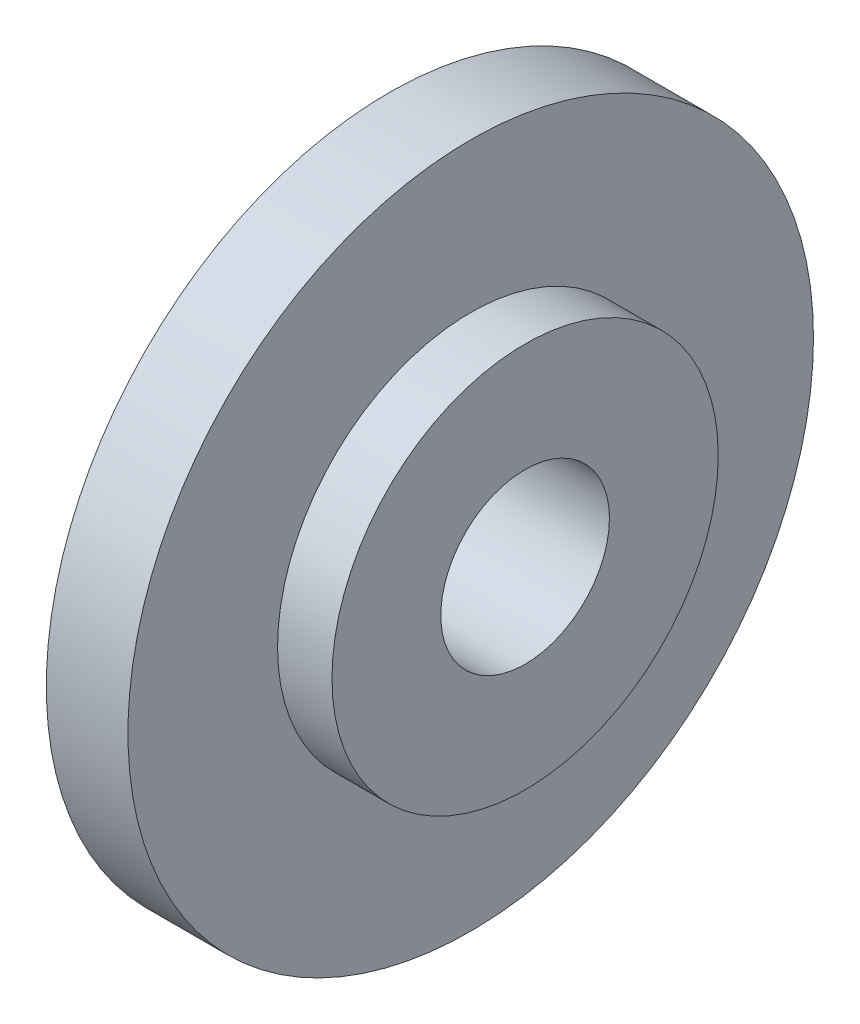
SolidWorks part; units mm, degrees
ref_plane "Front Plane" through (0, 0, 0) normal (0, 0, 1) x (1, 0, 0)
ref_plane "Top Plane" through (0, 0, 0) normal (0, 1, 0) x (1, 0, 0)
ref_plane "Right Plane" through (0, 0, 0) normal (1, 0, 0) x (0, 0, -1)
sketch "Sketch1" plane through (0, 0, 0) normal (1, 0, 0) x (0, 0, -1)
  circle A0 centre (0, 0) radius 12.6
  circle A1 centre (0, 0) radius 7.1
  circle A2 centre (0, 0) radius 3.1
  dimension "D1" = 6.2
  dimension "D2" = 4
  dimension "D3" = 5.5
extrude "Boss-Extrude1" add sketch "Sketch1" along normal blind 3 contours A0 A1 region at (0, 0, 12.2436)
extrude "Boss-Extrude2" add sketch "Sketch1<4>" along normal blind 5 contours A1 A2 region at (0, 0, 6.8992)
sketch "Sketch1<4>" plane through (0, 0, 0) normal (1, 0, 0) x (0, 0, -1) same geometry as "Sketch1"
